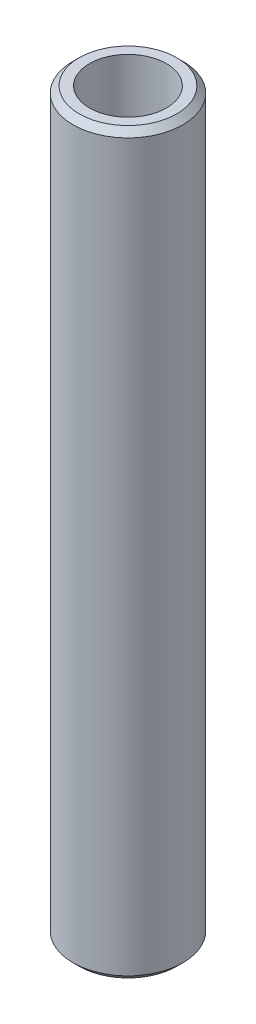
SolidWorks part; units mm, degrees
ref_plane "Front Plane" through (0, 0, 0) normal (0, 0, 1) x (1, 0, 0)
ref_plane "Top Plane" through (0, 0, 0) normal (0, 1, 0) x (1, 0, 0)
ref_plane "Right Plane" through (0, 0, 0) normal (1, 0, 0) x (0, 0, -1)
sketch "Sketch1" plane through (0, 0, 0) normal (0, 1, 0) x (1, 0, 0)
  circle A0 centre (0, 0) radius 32.5
  dimension "SHAFT_OD" = 65
extrude "Boss-Extrude1" add sketch "Sketch1" along normal blind 436.2338
sketch "Sketch2" plane through (0, 0, 0) normal (0, 1, 0) x (1, 0, 0)
  circle A0 centre (0, 0) radius 22.7457
  dimension "BORE_D" = 45.4913
extrude "Cut-Extrude1" cut sketch "Sketch2" along normal through all
chamfer "Chamfer1" distance 3.7073 angle 45 2 edges at (0, 436.2338, 32.5) (0, 0, 32.5)
